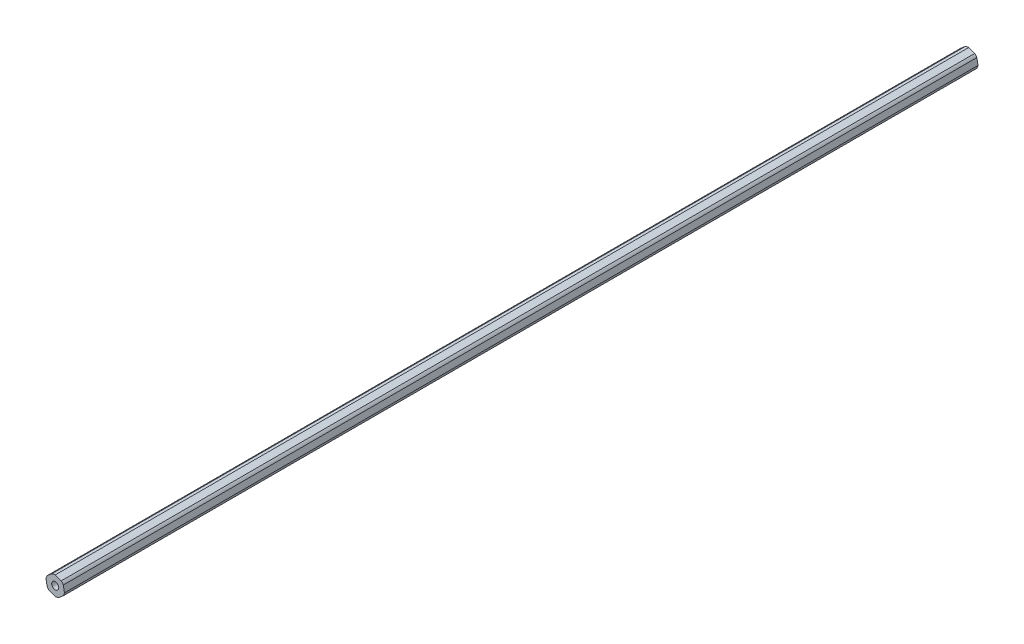
SolidWorks part; units mm, degrees
material "7075-T6 (SN)"
ref_plane "Front Plane" through (0, 0, 0) normal (0, 0, 1) x (1, 0, 0)
ref_plane "Top Plane" through (0, 0, 0) normal (0, 1, 0) x (1, 0, 0)
ref_plane "Right Plane" through (0, 0, 0) normal (1, 0, 0) x (0, 0, -1)
sketch "Sketch1" plane through (0, 0, 0) normal (0, 0, 1) x (1, 0, 0)
  line L1 (-6.6545, 1.1312) -> (-5.8457, -3.375)
  line L2 (-4.3069, -5.1974) -> (0, -6.75)
  line L3 (2.3476, -6.3286) -> (5.8457, -3.375)
  line L4 (6.6545, -1.1312) -> (5.8457, 3.375)
  line L5 (4.3069, 5.1974) -> (0, 6.75)
  line L6 (-2.3476, 6.3286) -> (-5.8457, 3.375)
  circle A0 centre (0, 0) radius 6.35 construction
  arc A1 (-5.8457, 3.375) -> (-6.6545, 1.1312) centre (0, 0) ccw
  arc A2 (-5.8457, -3.375) -> (-4.3069, -5.1974) centre (0, 0) ccw
  arc A3 (0, -6.75) -> (2.3476, -6.3286) centre (0, 0) ccw
  arc A4 (5.8457, -3.375) -> (6.6545, -1.1312) centre (0, 0) ccw
  arc A5 (5.8457, 3.375) -> (4.3069, 5.1974) centre (0, 0) ccw
  arc A6 (0, 6.75) -> (-2.3476, 6.3286) centre (0, 0) ccw
  dimension "D1" = 12.7
  dimension "D2" = 13.5
extrude "Boss-Extrude1" add sketch "Sketch1" along normal blind 659.0157
sketch "Sketch2" plane through (0, 0, 659.0157) normal (0, 0, 1) x (1, 0, 0)
  circle A0 centre (0, 0) radius 2.0193
  dimension "D1" = 4.0386
extrude "Cut-Extrude1" cut sketch "Sketch2" against normal through all
hole_wizard "1/4-20 Tapped Hole1" positions "Sketch5" profile "Sketch6" tap size "1/4-20" standard "ANSI Inch"
sketch "Sketch5" plane through (0, 0, 659.0157) normal (0, 0, 1) x (1, 0, 0)
  point P0 (0, 0)
sketch "Sketch6" plane through (0, 0, 659.0157) normal (1, 0, 0) x (0, -1, 0)
  line L0 (0, 0) -> (0, 20.5838)
  line L1 (0, 20.5838) -> (2.5527, 19.05)
  line L2 (2.5527, 19.05) -> (2.5527, 0)
  line L5 (2.5527, 0) -> (0, 0)
  line L10 (0, 20.5838) -> (-2.5527, 19.05) construction
  line L11 (0, -6.35) -> (0, 107.95) construction
  dimension "Tap Drill Dia." = 5.1054
  dimension "Tap Drill Depth" = 19.05
  dimension "Drill Angle" = 118
cosmetic thread "Hole Thread1" parameters "D1"=12.7, "D2"=6.35
hole_wizard "1/4-20 Tapped Hole2" positions "Sketch7" profile "Sketch8" tap size "1/4-20" standard "ANSI Inch"
sketch "Sketch7" plane through (0, 0, 0) normal (0, 0, -1) x (-1, 0, 0)
  point P0 (0, 0)
sketch "Sketch8" plane through (0, 0, 0) normal (1, 0, 0) x (0, 1, 0)
  line L0 (0, 0) -> (0, 20.5838)
  line L1 (0, 20.5838) -> (2.5527, 19.05)
  line L2 (2.5527, 19.05) -> (2.5527, 0)
  line L5 (2.5527, 0) -> (0, 0)
  line L10 (0, 20.5838) -> (-2.5527, 19.05) construction
  line L11 (0, -6.35) -> (0, 107.95) construction
  dimension "Tap Drill Dia." = 5.1054
  dimension "Tap Drill Depth" = 19.05
  dimension "Drill Angle" = 118
cosmetic thread "Hole Thread2" parameters "D1"=12.7, "D2"=6.35
